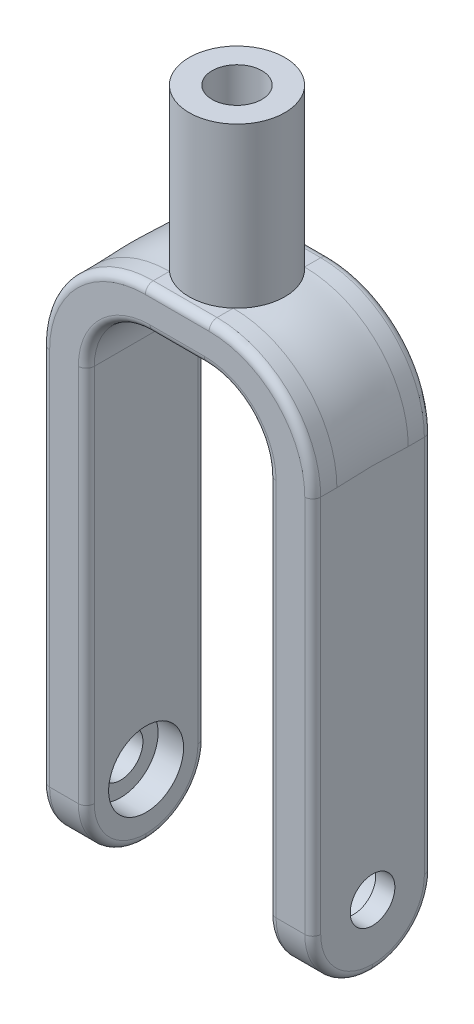
SolidWorks part; units mm, degrees
ref_plane "前视基准面" through (0, 0, 0) normal (0, 0, 1) x (1, 0, 0)
ref_plane "上视基准面" through (0, 0, 0) normal (0, 1, 0) x (1, 0, 0)
ref_plane "右视基准面" through (0, 0, 0) normal (1, 0, 0) x (0, 0, -1)
sketch "草图1" plane through (0, 0, 0) normal (0, 1, 0) x (1, 0, 0)
  line L1 (17, 7.5) -> (-17, 7.5)
  line L2 (17, 7.5) -> (17, -7.5)
  line L3 (17, -7.5) -> (-17, -7.5)
  line L4 (-17, 7.5) -> (-17, -7.5)
  line L5 (17, 7.5) -> (-17, -7.5) construction
  line L6 (17, -7.5) -> (-17, 7.5) construction
  point P0 (0, 0)
extrude "凸台-拉伸1" add sketch "草图1" against normal blind 68
sketch "草图2" plane through (0, 0, 0) normal (0, 1, 0) x (1, 0, 0)
  circle A0 centre (0, 0) radius 6
extrude "凸台-拉伸2" add sketch "草图2" along normal blind 20
sketch "草图7" plane through (0, 20, 0) normal (0, 1, 0) x (1, 0, 0)
  circle A0 centre (0, 0) radius 3.125
sketch "草图3" plane through (0, 0, 7.5) normal (0, 0, 1) x (1, 0, 0)
  line L0 (-17, -68) -> (17, -68) construction
  line L1 (-11.4, -68) -> (11.4, -68)
  line L2 (-11.4, -68) -> (-11.4, -5)
  line L3 (-11.4, -5) -> (11.4, -5)
  line L4 (11.4, -68) -> (11.4, -5)
extrude "切除-拉伸1" cut sketch "草图3" against normal through all
fillet "圆角1" radius 8 2 edges at (11.4, -5, 0) (-11.4, -5, 0)
fillet "圆角5" radius 13 2 edges at (17, 0, 0) (-17, 0, 0)
fillet "圆角3" radius 7.5 4 edges at (14.2, -68, -7.5) (14.2, -68, 7.5) (-14.2, -68, -7.5) (-14.2, -68, 7.5)
fillet "圆角2" radius 1 28 edges at (-17, -36.75, -7.5) (0, 0, -7.5) (17, -36.75, -7.5) (17, -36.75, 7.5) (0, 0, 7.5) (-17, -36.75, 7.5) (-9.0569, -7.3431, 7.5) (0, -5, 7.5) (9.0569, -7.3431, 7.5) (11.4, -36.75, 7.5) (11.4, -36.75, -7.5) (9.0569, -7.3431, -7.5) (0, -5, -7.5) (-9.0569, -7.3431, -7.5) (-11.4, -36.75, -7.5) (-11.4, -36.75, 7.5) (11.4, -65.8033, 5.3033) (11.4, -65.8033, -5.3033) (-11.4, -65.8033, -5.3033) (-11.4, -65.8033, 5.3033) (-17, -65.8033, 5.3033) (-17, -65.8033, -5.3033) (17, -65.8033, -5.3033) (17, -65.8033, 5.3033) (-13.1924, -3.8076, -7.5) (13.1924, -3.8076, -7.5) (13.1924, -3.8076, 7.5) (-13.1924, -3.8076, 7.5)
sketch "草图4" plane through (17, 0, 0) normal (1, 0, 0) x (0, 0, -1)
  circle A0 centre (0, -60) radius 2.8
extrude "切除-拉伸2" cut sketch "草图4" against normal through all
sketch "草图6" plane through (11.4, 0, 0) normal (1, 0, 0) x (0, 0, -1)
  circle A0 centre (0, -60) radius 4.7
extrude "切除-拉伸4" cut sketch "草图6" along normal blind 3.2
mirror "镜向1" about plane through (0, 0, 0) normal (1, 0, 0) of "切除-拉伸4"
extrude "切除-拉伸5" cut sketch "草图7" against normal blind 20
